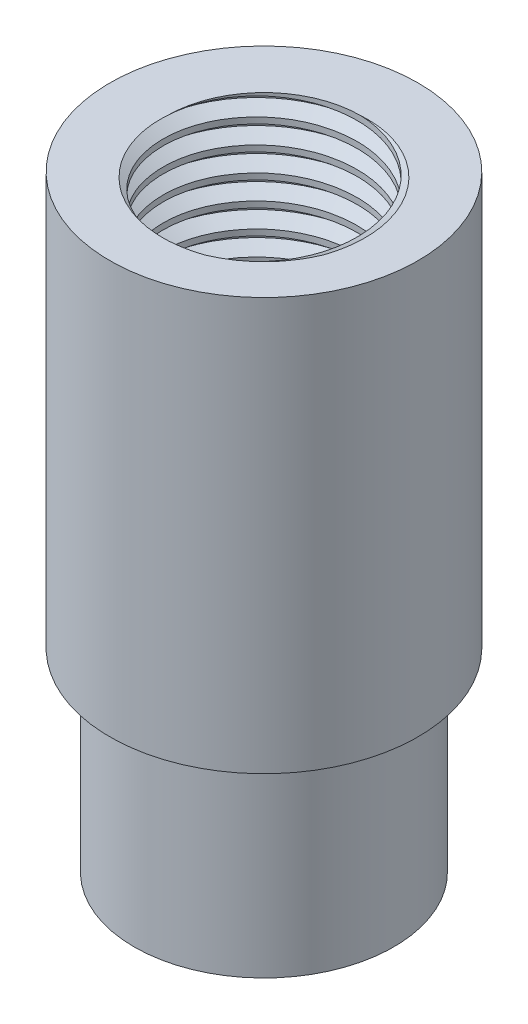
SolidWorks part; units mm, degrees
material "Alloy Steel"
ref_plane "Front Plane" through (0, 0, 0) normal (0, 0, 1) x (1, 0, 0)
ref_plane "Top Plane" through (0, 0, 0) normal (0, 1, 0) x (1, 0, 0)
ref_plane "Right Plane" through (0, 0, 0) normal (1, 0, 0) x (0, 0, -1)
sketch "Sketch1" plane through (0, 0, 0) normal (0, 0, 1) x (1, 0, 0)
  line L0 (0, 0) -> (0, 25)
  line L1 (0, 25) -> (6.35, 25)
  line L2 (6.35, 25) -> (6.35, 8)
  line L3 (6.35, 8) -> (5.35, 8)
  line L4 (5.35, 8) -> (5.35, 0)
  line L5 (5.35, 0) -> (0, 0)
  line L6 (4, 25) -> (4, 10)
  line L7 (4, 10) -> (0, 10)
  dimension "D1" = 25
  dimension "D2" = 8
  dimension "D3" = 1
  dimension "D4" = 6.35
  dimension "D5" = 15
  dimension "D6" = 4
revolve "Revolve1" add sketch "Sketch1" angle 360 about L0 region at (3.716, 9.9435, 0)
thread "Thread1" pitch 1 method cut profile "Thread Profile1" start angle 0, offset 2, length 17, pitch 1, diameter 8
ref_plane "Plane1" through (-4, 27, 0) normal (0, 0, 1) x (-1, 0, 0)
sketch "Thread Profile1" plane through (-4, 27, 0) normal (0, 0, 1) x (-1, 0, 0)
  line L0 (0, 0) -> (0, 1) construction
  line L1 (0, 0) -> (0.5413, 0.3125)
  line L2 (0.5413, 0.3125) -> (0.5413, 0.4375)
  line L3 (0.5413, 0.4375) -> (0, 0.75)
  line L4 (0.5413, 0.375) -> (0, 0.375) construction
  line L11 (0, 0) -> (0, 0.75)
  point P2 (0, 0)
  dimension "Pitch" = 1
  dimension "Profile_Angle" = 60
  dimension "Profile_Land" = 0.125
  dimension "Profile_Height" = 0.5413
